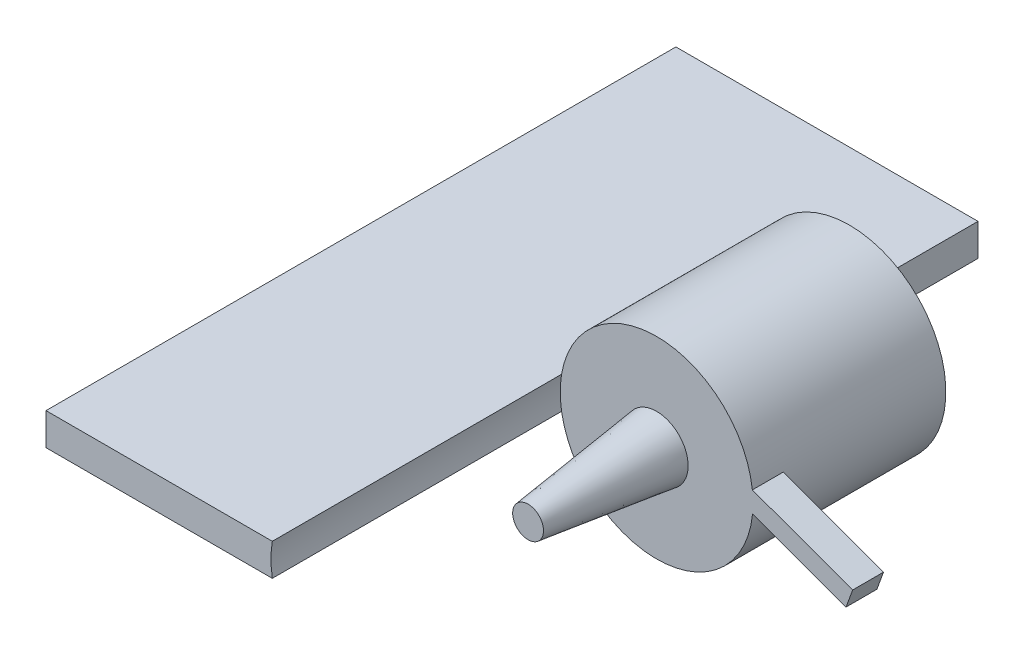
SolidWorks part; units mm, degrees
ref_plane "Front Plane" through (0, 0, 0) normal (0, 0, 1) x (1, 0, 0)
ref_plane "Top Plane" through (0, 0, 0) normal (0, 1, 0) x (1, 0, 0)
ref_plane "Right Plane" through (0, 0, 0) normal (1, 0, 0) x (0, 0, -1)
sketch "Sketch1" plane through (0, 0, 0) normal (0, 0, 1) x (1, 0, 0)
  line L0 (0, 0) -> (1.2826, 3.5238) construction
  line L5 (1.2826, 3.5238) -> (46.6088, -12.9735) construction
  line L6 (1.2826, 3.5238) -> (18.6539, -2.7988) construction
  line L7 (1.2826, 3.5238) -> (6.2305, 17.1183) construction
  line L8 (0, 0) -> (-31.7364, 0) construction
  line L9 (10.6795, 0.1036) -> (29.4734, -6.7368)
  line L10 (10.6795, 0.1036) -> (11.7056, 2.9227)
  line L11 (11.7056, 2.9227) -> (30.4994, -3.9177)
  line L12 (29.4734, -6.7368) -> (30.4994, -3.9177)
  line L13 (-3, 2.5) -> (-3, -2.5)
  line L14 (-50, 2.5) -> (0, 2.5)
  line L15 (-50, 2.5) -> (-50, -2.5)
  line L16 (-50, -2.5) -> (0, -2.5)
  line L17 (0, 2.5) -> (0, -2.5)
  circle A0 centre (0, 0) radius 4.9
  circle A1 centre (0, 0) radius 15
  circle A2 centre (0, 0) radius 2.4
  point P17 (-50, 0)
  point P18 (0, 0)
  dimension "D1" = 4.8
  dimension "D2" = 9.8
  dimension "D3" = 30
  dimension "D4" = 5
  dimension "D5" = 3.75
  dimension "D6" = 90
  dimension "D7" = 20
  dimension "D8" = 10
  dimension "D9" = 3
  dimension "D10" = 50
  dimension "D11" = 110
  dimension "D12" = 3
extrude "Boss-Extrude1" add sketch "Sketch1" against normal blind 15 and the other way blind 15 contours A1
extrude "Boss-Extrude2" add sketch "Sketch1<3>" against normal blind 4.8 from surface contours A2 starting at face at (15, 0, -15)
sketch "Sketch1<3>" plane through (0, 0, 0) normal (0, 0, 1) x (1, 0, 0) same geometry as "Sketch1"
ref_plane "Plane1" through (0, 0, 35) normal (0, 0, 1) x (1, 0, 0)
ref_plane "Plane2" through (0, 0, 15) normal (0, 0, 1) x (1, 0, 0)
sketch "Sketch4" plane through (0, 0, 15) normal (0, 0, 1) x (1, 0, 0)
  circle A0 centre (0, 0) radius 4.9
  circle A1 centre (0, 0) radius 4.9 construction
sketch "Sketch3" plane through (0, 0, 35) normal (0, 0, 1) x (1, 0, 0)
  circle A0 centre (0, 0) radius 2.4
  dimension "D1" = 4.8
loft "Loft2" add section "Sketch4" section "Sketch3" connector at (0.2431, 4.894, 15) connector at (0.2903, 2.3824, 35)
extrude "Boss-Extrude3" add sketch "Sketch1<5>" against normal blind 4.8 from surface contours L11 L12 L9 L10 starting at face at (15, 0, 15)
sketch "Sketch1<5>" plane through (0, 0, 0) normal (0, 0, 1) x (1, 0, 0) same geometry as "Sketch1"
extrude "Boss-Extrude4" add sketch "Sketch1<7>" along normal blind 60 contours A1 L14 L15 L16 region at (-32.4651, 0, 0)
sketch "Sketch1<7>" plane through (0, 0, 0) normal (0, 0, 1) x (1, 0, 0) same geometry as "Sketch1"
extrude "Boss-Extrude5" add sketch "Sketch1<8>" against normal blind 38 contours A1 L14 L15 L16 | L14 A1 L16 A0 | A2 L13 L14 A0 L16 region at (-9.8024, 0, 0) region at (-32.4651, 0, 0) region at (-3.8513, 0, 0)
sketch "Sketch1<8>" plane through (0, 0, 0) normal (0, 0, 1) x (1, 0, 0) same geometry as "Sketch1"
sketch "Sketch6" plane through (0, 0, 0) normal (0, 1, 0) x (1, 0, 0)
  line L0 (0, 37.34) -> (0, -60) construction
  line L1 (0, -60) -> (-85.7697, -10.4809) construction
  line L2 (-8.8335, -54.9) -> (-21.8677, 19.0206) construction
  line L3 (-7.0955, 21.6253) -> (0, 37.34) construction
  line L5 (-15, -60) -> (-14.7902, -60) construction
  line L6 (-25.7912, -45.1094) -> (-36.6398, 16.4159) construction
  line L7 (-7.0955, 21.6253) -> (-36.6398, 16.4159) construction
  point P14 (-21.8677, 19.0206)
  dimension "D1" = 60
  dimension "D2" = 50
  dimension "D3" = 10.2
  dimension "D4" = 57.5
  dimension "D5" = 30
  dimension "D6" = 97.34
sketch "Sketch7" plane through (0, 0, 0) normal (0, 1, 0) x (1, 0, 0)
  line L0 (-25.7912, -45.1094) -> (0, -60)
  line L1 (0, -60) -> (-85.7697, -10.4809) construction
  line L2 (-25.7912, -45.1094) -> (-36.6398, 16.4159) construction
  line L3 (-25.7912, -45.1094) -> (-36.6398, 16.4159)
  line L4 (-36.6398, 16.4159) -> (-7.0955, 21.6253)
  line L5 (-7.0955, 21.6253) -> (0, 37.34)
  line L6 (0, 37.34) -> (0, 57.9952)
  line L7 (0, 57.9952) -> (-77.2907, 57.9952)
  line L8 (-77.2907, 57.9952) -> (-77.2907, -86.6864)
  line L9 (-77.2907, -86.6864) -> (0, -86.6864)
  line L10 (0, -86.6864) -> (0, -60)
  point P19 (0, 0)
  point P20 (0, 0)
